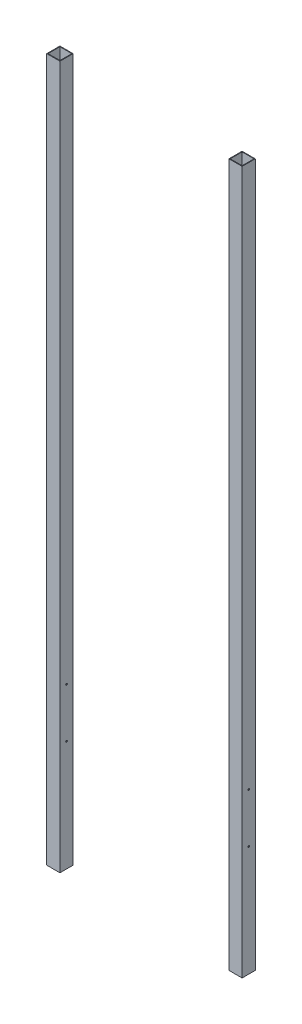
SolidWorks part; units mm, degrees
ref_plane "Front Plane" through (0, 0, 0) normal (0, 0, 1) x (1, 0, 0)
ref_plane "Top Plane" through (0, 0, 0) normal (0, 1, 0) x (1, 0, 0)
ref_plane "Right Plane" through (0, 0, 0) normal (1, 0, 0) x (0, 0, -1)
sketch "Sketch1" plane through (0, 0, 0) normal (0, 1, 0) x (1, 0, 0)
  line L0 (32.258, 0) -> (0, 32.258) construction
  line L1 (0, 0) -> (32.258, 0)
  line L2 (0, 0) -> (0, 32.258)
  line L3 (0, 32.258) -> (32.258, 32.258)
  line L4 (32.258, 0) -> (32.258, 32.258)
  line L5 (33.909, -1.651) -> (33.909, 33.909)
  line L6 (-1.651, 33.909) -> (33.909, 33.909)
  line L7 (-1.651, -1.651) -> (-1.651, 33.909)
  line L8 (-1.651, -1.651) -> (33.909, -1.651)
  line L9 (16.129, 16.129) -> (508.254, 16.129) construction
  line L11 (490.474, -1.651) -> (526.034, -1.651)
  line L12 (490.474, -1.651) -> (490.474, 33.909)
  line L13 (490.474, 33.909) -> (526.034, 33.909)
  line L14 (526.034, -1.651) -> (526.034, 33.909)
  line L15 (490.474, -1.651) -> (526.034, 33.909) construction
  line L16 (490.474, 33.909) -> (526.034, -1.651) construction
  line L17 (492.125, 0) -> (524.383, 0)
  line L18 (492.125, 0) -> (492.125, 32.258)
  line L19 (492.125, 32.258) -> (524.383, 32.258)
  line L20 (524.383, 0) -> (524.383, 32.258)
  line L21 (492.125, 0) -> (524.383, 32.258) construction
  line L22 (492.125, 32.258) -> (524.383, 0) construction
  dimension "D1" = 32.258
  dimension "D2" = 1.651
  dimension "D3" = 492.125
extrude "Boss-Extrude1" add sketch "Sketch1" along normal blind 1898.65
hole_wizard "#8 Clearance Hole1" positions "Sketch2" profile "Sketch4" hole size "#8" standard "ANSI Inch" end condition through all
sketch "Sketch2" plane through (526.034, 0, 0) normal (1, 0, 0) x (0, 0, -1)
  line L0 (16.129, 1898.65) -> (16.129, 162.306) construction
  line L1 (-1.651, 1898.65) -> (33.909, 1898.65) construction
  line L2 (-2.921, 162.306) -> (35.179, 162.306) construction
  line L4 (-1.651, 0) -> (33.909, 0) construction
  point P8 (16.129, 431.8)
  point P10 (16.129, 298.45)
  dimension "D1" = 298.45
  dimension "D2" = 133.35
sketch "Sketch4" plane through (526.034, 298.45, -16.129) normal (0, 1, 0) x (0, 0, -1)
  line L0 (0, 0) -> (0, 527.685)
  line L1 (0, 527.685) -> (2.1526, 527.685)
  line L2 (2.1526, 527.685) -> (2.1526, 0)
  line L5 (2.1526, 0) -> (0, 0)
  line L11 (0, -6.35) -> (0, 107.95) construction
  dimension "Thru Hole Dia." = 4.3053
  dimension "Thru Hole Depth" = 527.685
